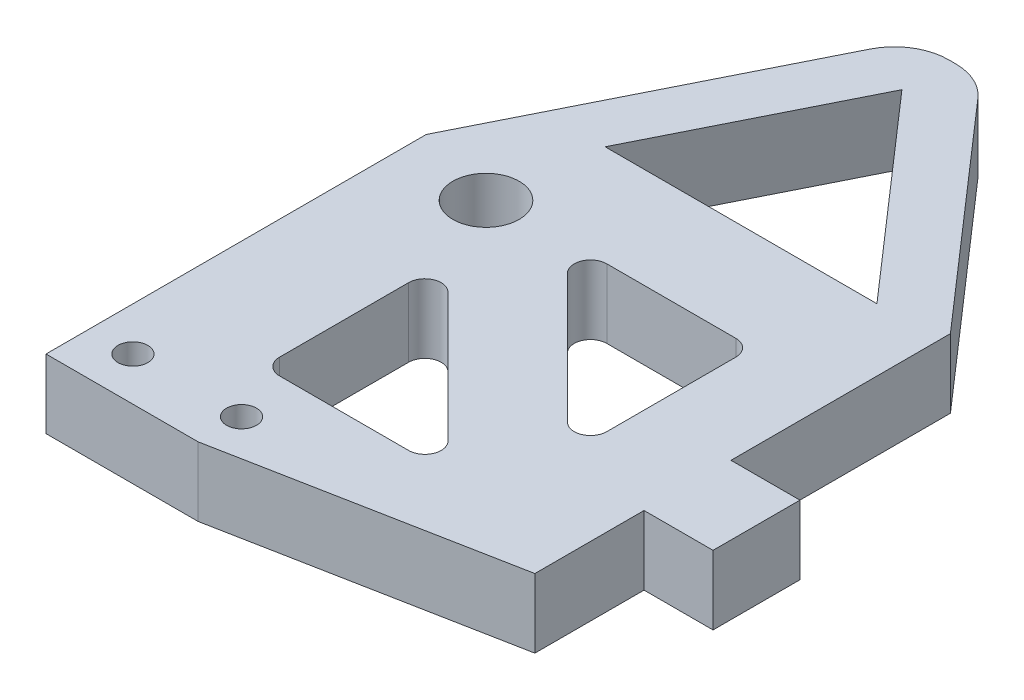
SolidWorks part; units mm, degrees
material "6061 Alloy"
ref_plane "Front Plane" through (0, 0, 0) normal (0, 0, 1) x (1, 0, 0)
ref_plane "Top Plane" through (0, 0, 0) normal (0, 1, 0) x (1, 0, 0)
ref_plane "Right Plane" through (0, 0, 0) normal (1, 0, 0) x (0, 0, -1)
sketch "Sketch1" plane through (0, 0, 0) normal (0, 1, 0) x (1, 0, 0)
  line L1 (-80, 0) -> (-80, 60)
  line L7 (0, 0) -> (-52, -10)
  line L8 (-52, -10) -> (-80, -10)
  line L9 (-80, -10) -> (-80, 0)
  line L10 (-80, 60) -> (-50, 120)
  line L11 (-50, 120) -> (-38, 120)
  line L12 (-38, 120) -> (0, 76.5)
  line L13 (0, 76.5) -> (0, 36.1)
  line L14 (0, 36.1) -> (12.7, 36.1)
  line L15 (12.7, 36.1) -> (12.7, 20.1)
  line L16 (12.7, 20.1) -> (0, 20.1)
  line L17 (0, 20.1) -> (0, 0)
  circle A0 centre (-64, 55) radius 6.1
  circle A3 centre (-72, -2) radius 2.75
  circle A4 centre (-52, -2) radius 2.75
  dimension "D8" = 12.2
  dimension "D12" = 5.5
  dimension "D16" = 5.5
  dimension "D1" = 80
  dimension "D2" = 76.5
  dimension "D3" = 60
  dimension "D9" = 16
  dimension "D14" = 8
  dimension "D15" = 20
  dimension "D10" = 10
  dimension "D13" = 8
  dimension "D17" = 55
  dimension "D4" = 60
  dimension "D5" = 30
  dimension "D6" = 12
  dimension "D7" = 20.1
  dimension "D18" = 12.7
  dimension "D11" = 16
extrude "Boss-Extrude1" add sketch "Sketch1" along normal blind 12.7
fillet "Fillet1" radius 10 2 edges at (-38, 6.35, -120) (-50, 6.35, -120)
sketch "Sketch3" plane through (0, 12.7, 0) normal (0, 1, 0) x (1, 0, 0)
  line L5 (-11.5311, 74.5) -> (-43.3548, 110.9297)
  line L6 (-43.3548, 110.9297) -> (-61.5697, 74.5)
  line L7 (-61.5697, 74.5) -> (-11.5311, 74.5)
  line L8 (-58, 34.7574) -> (-58, 11)
  line L9 (-55, 8) -> (-31.2426, 8)
  line L10 (0, 76.5) -> (-35.0115, 116.5789) construction
  line L11 (-52.7639, 114.4721) -> (-80, 60) construction
  line L12 (-29.1213, 13.1213) -> (-52.8787, 36.8787)
  line L13 (-16, 29.2426) -> (-16, 53)
  line L14 (-19, 56) -> (-42.7574, 56)
  line L15 (-44.8787, 50.8787) -> (-21.1213, 27.1213)
  line L16 (-80, 60) -> (-80, -10) construction
  line L17 (-80, -10) -> (-52, -10) construction
  arc A0 (-16, 53) -> (-19, 56) centre (-19, 53) ccw
  arc A1 (-44.8787, 50.8787) -> (-42.7574, 56) centre (-42.7574, 53) cw
  arc A2 (-16, 29.2426) -> (-21.1213, 27.1213) centre (-19, 29.2426) cw
  arc A3 (-31.2426, 8) -> (-29.1213, 13.1213) centre (-31.2426, 11) ccw
  arc A4 (-55, 8) -> (-58, 11) centre (-55, 11) cw
  arc A5 (-58, 34.7574) -> (-52.8787, 36.8787) centre (-55, 34.7574) cw
  point P21 (-16, 56)
  point P24 (-50, 56)
  point P27 (-16, 22)
  point P30 (-24, 8)
  point P33 (-58, 8)
  point P36 (-58, 42)
  dimension "D14" = 3
  dimension "D1" = 10
  dimension "D2" = 10
  dimension "D3" = 10
  dimension "D4" = 10
  dimension "D5" = 2
  dimension "D6" = 22
  dimension "D7" = 18
  dimension "D8" = 34
  dimension "D9" = 34
  dimension "D10" = 64
  dimension "D11" = 32
  dimension "D12" = 34
  dimension "D13" = 34
extrude "Cut-Extrude1" cut sketch "Sketch3" against normal through all
fillet "Fillet2" [suppressed] radius 5
equation "\"DriveMotorLength\"= 90mm"
equation "\"DriveMotorGap\"= 10mm"
equation "\"AluminumThickness\"= 0.5in"
equation "\"ChassisWidth\"= ( \"DriveMotorLength\" + \"AluminumThickness\" ) * 2 + \"DriveMotorGap\""
equation "\"RepeatMagnumHoleWidth\"= 19.05mm"
equation "\"MortiseWidth\"= 16mm"
equation "\"ChassisScrewThruHole\"= 5.5mm"
equation "\"D12@Sketch1\"=\"ChassisScrewThruHole\""
equation "\"D16@Sketch1\"=\"ChassisScrewThruHole\""
equation "\"MortiseSlotWidth\"= 16.2mm"
equation "\"D11@Sketch1\"=\"MortiseWidth\""
